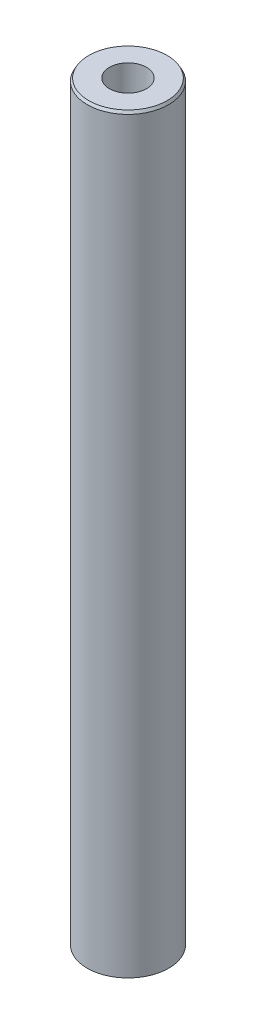
SolidWorks part; units mm, degrees
ref_plane "Front Plane" through (0, 0, 0) normal (0, 0, 1) x (1, 0, 0)
ref_plane "Top Plane" through (0, 0, 0) normal (0, 1, 0) x (1, 0, 0)
ref_plane "Right Plane" through (0, 0, 0) normal (1, 0, 0) x (0, 0, -1)
sketch "Sketch1" plane through (0, 0, 0) normal (0, 1, 0) x (1, 0, 0)
  circle A0 centre (0, 0) radius 32.5
  dimension "SHAFT_OD" = 65
extrude "Boss-Extrude1" add sketch "Sketch1" along normal blind 600
sketch "Sketch2" plane through (0, 0, 0) normal (0, 1, 0) x (1, 0, 0)
  circle A0 centre (0, 0) radius 14.8022
  dimension "BORE_D" = 29.6045
extrude "Cut-Extrude1" cut sketch "Sketch2" along normal through all
chamfer "Chamfer1" distance 2.182 angle 29.6 2 edges at (0, 600, 32.5) (0, 0, 32.5) first distance on face at (0, 600, 32.5) first distance on face at (0, 0, 14.8022)
